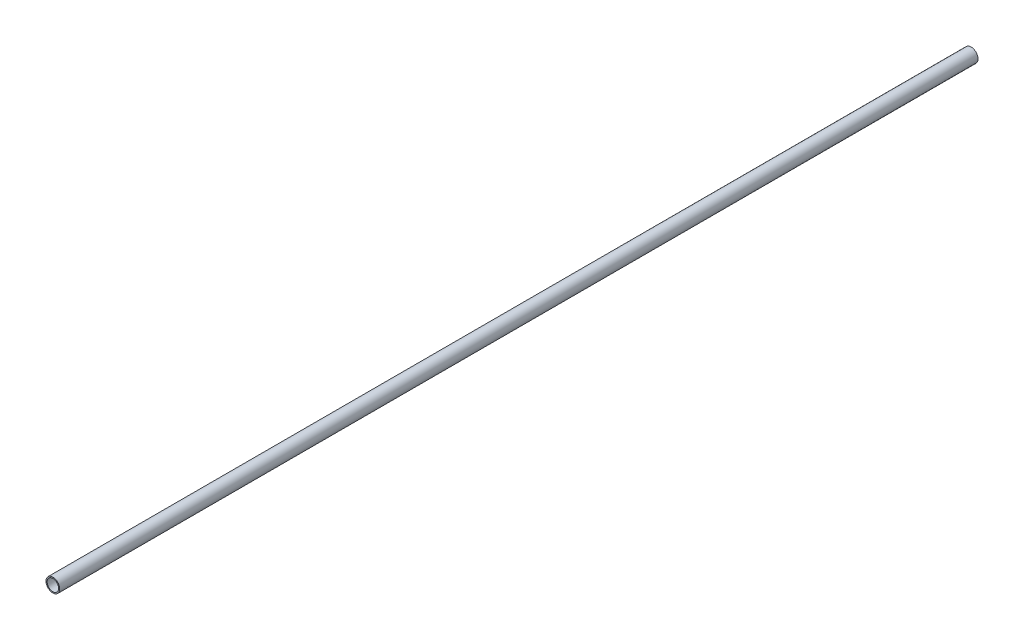
SolidWorks part; units mm, degrees
material "1060 Alloy"
ref_plane "Front Plane" through (0, 0, 0) normal (0, 0, 1) x (1, 0, 0)
ref_plane "Top Plane" through (0, 0, 0) normal (0, 1, 0) x (1, 0, 0)
ref_plane "Right Plane" through (0, 0, 0) normal (1, 0, 0) x (0, 0, -1)
sketch "Sketch1" plane through (0, 0, 0) normal (0, 0, 1) x (1, 0, 0)
  circle A0 centre (0, 0) radius 6
  circle A1 centre (0, 0) radius 5
  dimension "D1" = 12
  dimension "D2" = 1
extrude "Boss-Extrude1" add sketch "Sketch1" along normal blind 800
ref_axis "Axis1" through (0, 0, 800) along (0, 0, -1)
sketch "Sketch2" plane through (0, 0, 0) normal (0, 1, 0) x (1, 0, 0)
  line L0 (0, -800) -> (0, 0) construction
  line L1 (0, 0) -> (0, -800) construction
  circle A0 centre (0, -240) radius 5
  circle A1 centre (0, -560) radius 5
  dimension "D1" = 10
  dimension "D2" = 240
  dimension "D3" = 240
